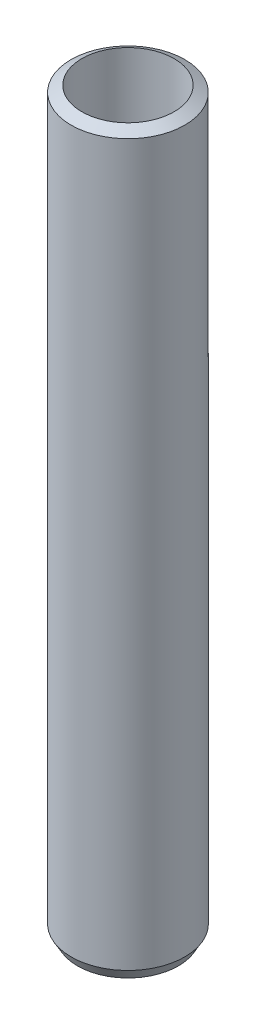
SolidWorks part; units mm, degrees
ref_plane "Front Plane" through (0, 0, 0) normal (0, 0, 1) x (1, 0, 0)
ref_plane "Top Plane" through (0, 0, 0) normal (0, 1, 0) x (1, 0, 0)
ref_plane "Right Plane" through (0, 0, 0) normal (1, 0, 0) x (0, 0, -1)
sketch "Sketch1" plane through (0, 0, 0) normal (0, 1, 0) x (1, 0, 0)
  circle A0 centre (0, 0) radius 35
  dimension "SHAFT_OD" = 70
extrude "Boss-Extrude1" add sketch "Sketch1" along normal blind 454.2229
sketch "Sketch2" plane through (0, 0, 0) normal (0, 1, 0) x (1, 0, 0)
  circle A0 centre (0, 0) radius 28.3993
  dimension "BORE_D" = 56.7986
extrude "Cut-Extrude1" cut sketch "Sketch2" along normal through all
chamfer "Chamfer1" distance 3.9213 angle 60 2 edges at (0, 454.2229, 35) (0, 0, 35) first distance on face at (0, 454.2229, 35) first distance on face at (0, 0, 28.3993)
